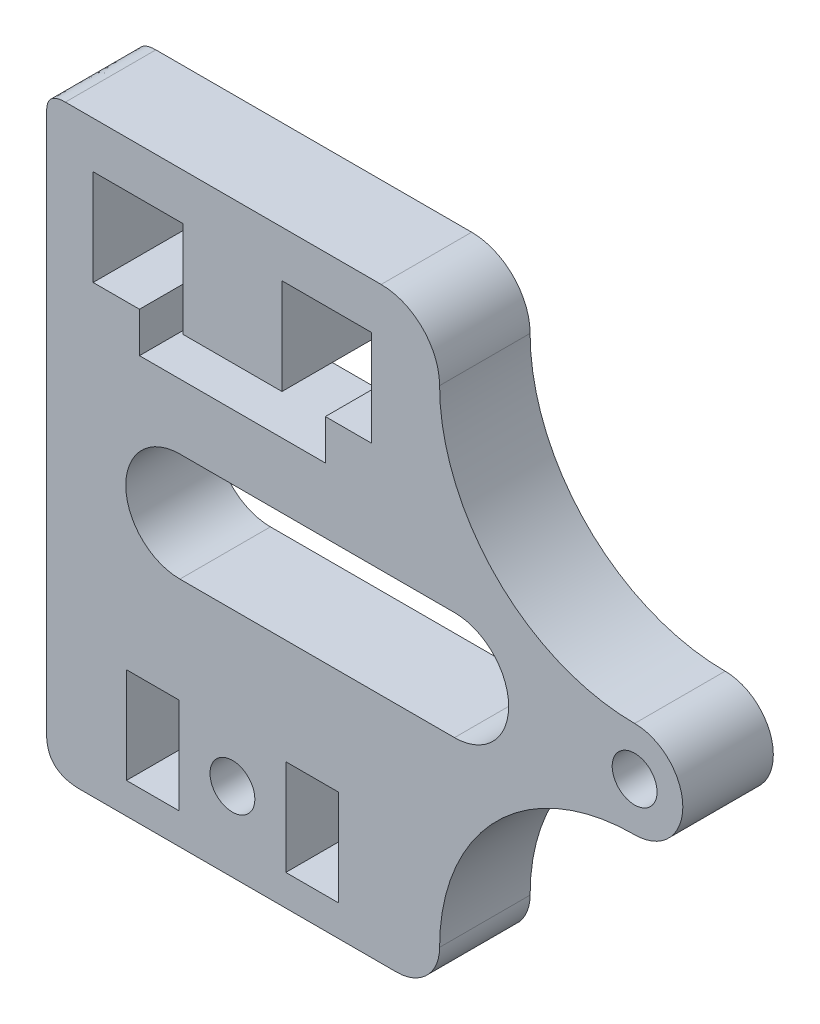
SolidWorks part; units mm, degrees
material "Acrylic (Medium-high impact)"
ref_plane "Front Plane" through (0, 0, 0) normal (0, 0, 1) x (1, 0, 0)
ref_plane "Top Plane" through (0, 0, 0) normal (0, 1, 0) x (1, 0, 0)
ref_plane "Right Plane" through (0, 0, 0) normal (1, 0, 0) x (0, 0, -1)
sketch "Sketch1" plane through (0, 0, 0) normal (0, 0, 1) x (1, 0, 0)
  line L0 (405.5669, 552.3389) -> (405.5669, 554.9389)
  line L1 (396.3551, 554.9389) -> (402.763, 554.9389)
  line L2 (393.5512, 554.9389) -> (393.5512, 552.3389)
  line L3 (393.5512, 552.3389) -> (405.5669, 552.3389)
  line L4 (390.5551, 561.1389) -> (390.5551, 554.9389)
  line L5 (393.5512, 554.9389) -> (390.5551, 554.9389)
  line L6 (396.3551, 561.1389) -> (390.5551, 561.1389)
  line L7 (396.3551, 554.9389) -> (396.3551, 561.1389)
  line L8 (405.5669, 554.9389) -> (408.563, 554.9389)
  line L9 (408.563, 554.9389) -> (408.563, 561.1389)
  line L10 (402.763, 561.1389) -> (402.763, 554.9389)
  line L11 (408.563, 561.1389) -> (402.763, 561.1389)
  line L12 (392.709, 534.3389) -> (392.709, 528.1389)
  line L13 (392.709, 528.1389) -> (396.109, 528.1389)
  line L14 (396.109, 534.3389) -> (392.709, 534.3389)
  line L15 (396.109, 528.1389) -> (396.109, 534.3389)
  line L16 (403.009, 528.1389) -> (406.4091, 528.1389)
  line L17 (406.4091, 528.1389) -> (406.4091, 534.3389)
  line L18 (403.009, 534.3389) -> (403.009, 528.1389)
  line L19 (406.4091, 534.3389) -> (403.009, 534.3389)
  line L20 (388.76, 564.1389) -> (409.1746, 564.1389)
  line L21 (387.5551, 562.9353) -> (387.5551, 528.3415)
  line L22 (389.76, 526.1389) -> (410.1746, 526.1389)
  line L23 (-606.039, 561.1389) -> (49393.961, 561.1389) construction
  line L24 (396.1657, 548.1389) -> (413.9157, 548.1389)
  line L25 (396.1657, 541.1389) -> (413.9157, 541.1389)
  line L26 (-600.441, 544.6389) -> (49399.559, 544.6389) construction
  line L27 (398.109, 531.2389) -> (396.109, 531.2389) construction
  line L28 (401.009, 531.2389) -> (403.009, 531.2389) construction
  line L29 (399.559, -466.6171) -> (399.559, 49533.3829) construction
  line L30 (425.559, -455.7473) -> (425.559, 49544.2527) construction
  line L31 (-599.1986, 528.1389) -> (49400.8014, 528.1389) construction
  line L32 (421.909, 544.6389) -> (421.909, 528.1389) construction
  line L33 (421.909, 544.6389) -> (421.909, 561.1389) construction
  line L34 (412.9514, 560.3621) -> (412.9514, 528.9157) construction
  circle A0 centre (425.559, 544.6389) radius 1.45
  arc A1 (396.1657, 548.1389) -> (396.1657, 541.1389) centre (396.1657, 544.6389) ccw
  circle A2 centre (399.559, 531.2389) radius 1.45
  arc A3 (412.9514, 528.9157) -> (425.559, 541.5233) centre (425.559, 528.9157) cw
  arc A4 (412.9514, 560.3621) -> (425.559, 547.7545) centre (425.559, 560.3621) ccw
  arc A5 (425.559, 547.7545) -> (425.559, 541.5233) centre (425.559, 544.6389) cw
  arc A7 (413.9157, 548.1389) -> (413.9157, 541.1389) centre (413.9157, 544.6389) cw
  arc A8 (410.1746, 526.1389) -> (412.9514, 528.9157) centre (410.1746, 528.9157) ccw
  arc A9 (409.1746, 564.1389) -> (412.9514, 560.3621) centre (409.1746, 560.3621) cw
  spline S36 degree 2 poles (387.5551, 562.9353) (387.4888, 564.1389) (388.76, 564.1389) knots 0 0 0 1 1 1
  spline S37 degree 2 poles (387.5551, 528.3415) (387.4338, 526.1389) (389.76, 526.1389) knots 0 0 0 1 1 1
  point P26 (399.559, 544.6389)
  point P30 (399.559, 554.9389)
  point P40 (412.9514, 544.6389)
  dimension "D5" = 2.9
  dimension "D12" = 6.2
  dimension "D2" = 3.4
  dimension "D3" = 5.8
  dimension "D4" = 2.6
  dimension "D6" = 2
  dimension "D7" = 33
  dimension "D8" = 2
  dimension "D9" = 3
  dimension "D10" = 3
  dimension "D11" = 26
  dimension "D13" = 12.0157
  dimension "D14" = 34.5937
  dimension "D15" = 31.4465
  dimension "D16" = 20.4146
  dimension "D17" = 17.75
  dimension "D19" = 13.3924
  dimension "D20" = 22.35
  dimension "D21" = 7
extrude "Boss-Extrude2" add sketch "Sketch1" along normal blind 5.85
